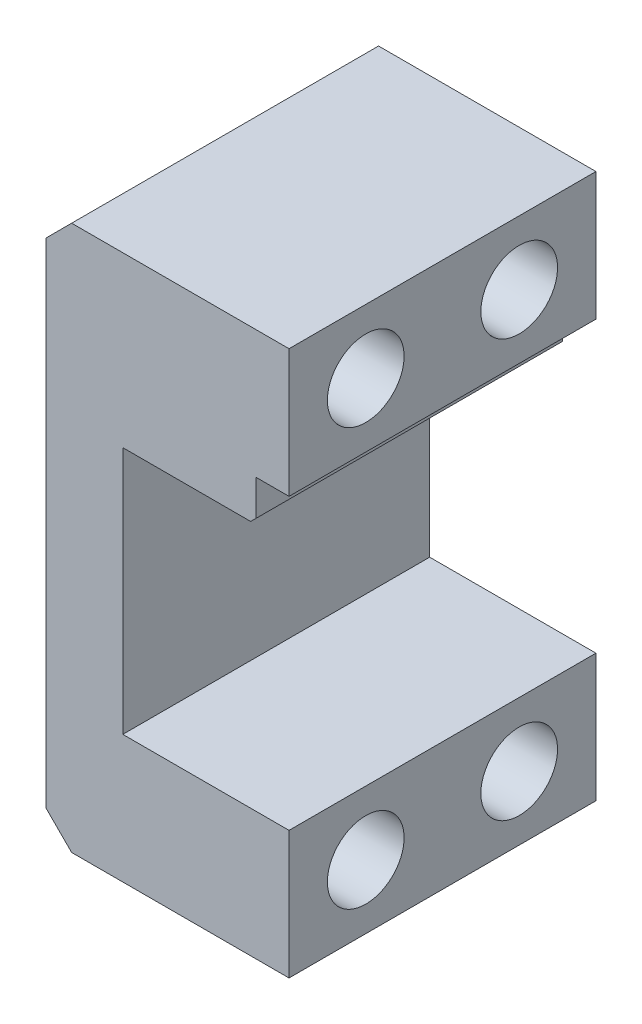
SolidWorks part; units mm, degrees
material "AISI 304"
ref_plane "前视基准面" through (0, 0, 0) normal (0, 0, 1) x (1, 0, 0)
ref_plane "上视基准面" through (0, 0, 0) normal (0, 1, 0) x (1, 0, 0)
ref_plane "右视基准面" through (0, 0, 0) normal (1, 0, 0) x (0, 0, -1)
sketch "草图1" plane through (0, 0, 0) normal (0, 0, 1) x (1, 0, 0)
  line L0 (0, 0) -> (0, 21.31)
  line L1 (0, 21.31) -> (9.5, 21.31)
  line L2 (9.5, 21.31) -> (9.5, 16.31)
  line L3 (9.5, 16.31) -> (8.2, 16.31)
  line L4 (8.2, 16.31) -> (8.2, 14.71)
  line L5 (8.2, 14.71) -> (3, 14.71)
  line L6 (3, 14.71) -> (3, 5)
  line L7 (3, 5) -> (9.5, 5)
  line L8 (9.5, 5) -> (9.5, 0)
  line L9 (9.5, 0) -> (0, 0)
  line L10 (9.5, 5) -> (9.5, 16.31) construction
  dimension "D1" = 5
  dimension "D2" = 9.71
  dimension "D3" = 3
  dimension "D4" = 1.3
  dimension "D5" = 6.5
  dimension "D6" = 1.6
  dimension "D7" = 5
extrude "凸台-拉伸1" add sketch "草图1" along normal blind 12
chamfer "倒角1" distance 0.2 angle 45 1 edges at (8.2, 14.71, 6)
sketch "草图2" plane through (0, 0, 0) normal (-1, 0, 0) x (0, 0, 1)
  line L0 (6, 21.31) -> (6, 0) construction
  line L1 (12, 21.31) -> (0, 21.31) construction
  line L2 (12, 0) -> (0, 0) construction
  line L3 (3, 18.81) -> (9, 18.81) construction
  line L4 (3, 2.5) -> (9, 2.5) construction
  line L5 (9, 2.5) -> (9, 18.81) construction
  line L6 (12, 21.31) -> (12, 0) construction
  circle A0 centre (9, 18.81) radius 1.5
  circle A1 centre (3, 18.81) radius 1.5
  circle A2 centre (3, 2.5) radius 1.5
  circle A3 centre (9, 2.5) radius 1.5
  point P9 (6, 18.81)
  point P12 (6, 2.5)
  dimension "D3" = 3
  dimension "D1" = 2.5
  dimension "D2" = 2.5
  dimension "D4" = 3
extrude "切除-拉伸1" cut sketch "草图2" against normal through all
chamfer "倒角2" distance 1 angle 45 2 edges at (0, 0, 6) (0, 21.31, 6)
